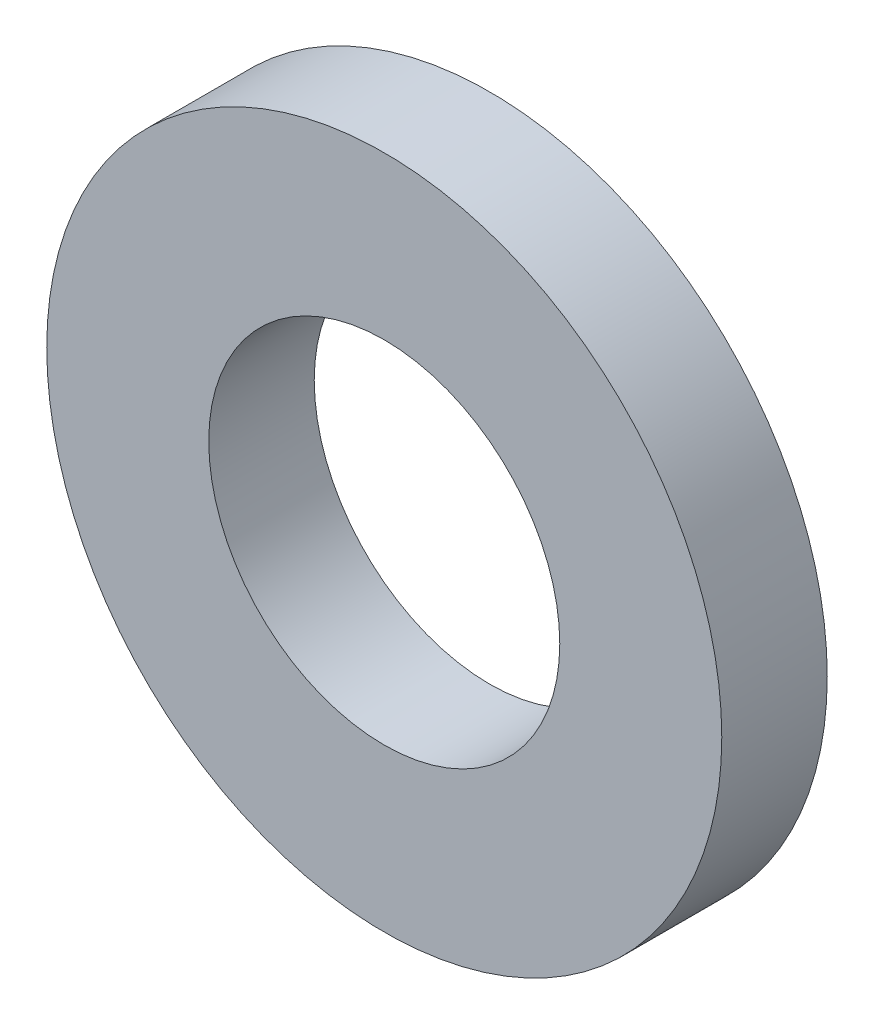
SolidWorks part; units mm, degrees
material "Nylon 101"
ref_plane "Front Plane" through (0, 0, 0) normal (0, 0, 1) x (1, 0, 0)
ref_plane "Top Plane" through (0, 0, 0) normal (0, 1, 0) x (1, 0, 0)
ref_plane "Right Plane" through (0, 0, 0) normal (1, 0, 0) x (0, 0, -1)
sketch "Sketch1" plane through (0, 0, 0) normal (0, 0, 1) x (1, 0, 0)
  circle A0 centre (0, 0) radius 6.604
  circle A1 centre (0, 0) radius 12.7
  dimension "D1" = 13.208
  dimension "D2" = 25.4
extrude "Boss-Extrude1" add sketch "Sketch1" along normal mid plane 3.9688
